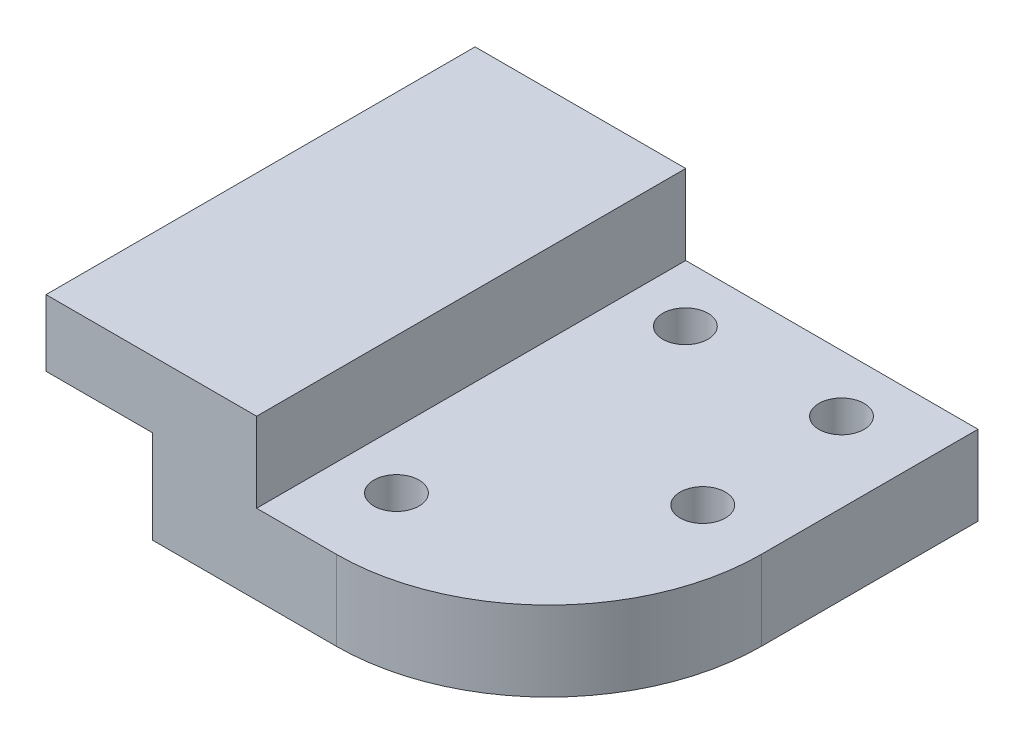
SolidWorks part; units mm, degrees
ref_plane "Front Plane" through (0, 0, 0) normal (0, 0, 1) x (1, 0, 0)
ref_plane "Top Plane" through (0, 0, 0) normal (0, 1, 0) x (1, 0, 0)
ref_plane "Right Plane" through (0, 0, 0) normal (1, 0, 0) x (0, 0, -1)
sketch "Sketch1" plane through (0, 0, 0) normal (0, 0, 1) x (1, 0, 0)
  line L0 (0, 0) -> (0, 3)
  line L1 (0, 3) -> (4, 3)
  line L3 (4, 0) -> (0, 0)
  line L4 (4, 3) -> (7.9273, 3)
  line L5 (7.9273, 3) -> (7.9273, 0)
  line L6 (7.9273, 0) -> (15.9273, 0)
  line L8 (15.9273, -3) -> (7.9273, -3)
  line L9 (7.9273, -3) -> (4, -3)
  line L10 (4, -3) -> (4, 0)
  line L11 (15.9273, 0) -> (15.9273, -3)
  dimension "D1" = 4
  dimension "D3" = 3
  dimension "D4" = 8
extrude "Boss-Extrude1" add sketch "Sketch1" along normal blind 20
ref_plane "Plane1" through (0, 0, 0) normal (0, 1, 0) x (1, 0, 0)
sketch "Sketch3" plane through (0, 0, 0) normal (0, 1, 0) x (1, 0, 0)
  line L0 (15.9273, -20) -> (15.9273, 0) construction
  line L1 (7.9273, -20) -> (15.9273, -20)
  line L2 (7.9273, -20) -> (7.9273, -12)
  line L3 (7.9273, -12) -> (15.9273, -12)
  line L4 (15.9273, -20) -> (15.9273, -12)
  dimension "D1" = 8
extrude "Cut-Extrude1" cut sketch "Sketch3" against normal blind 10
sketch "Sketch4" plane through (0, 0, 0) normal (0, 1, 0) x (1, 0, 0)
  line L0 (15.9273, -12) -> (7.9273, -12) construction
  circle A0 centre (11.9397, -3) radius 1
  circle A1 centre (11.9397, -9) radius 1
  dimension "D1" = 6
  dimension "D2" = 3
extrude "Cut-Extrude2" cut sketch "Sketch4" against normal blind 10
sketch "Sketch5" plane through (0, 0, 0) normal (0, -1, 0) x (1, 0, 0)
  line L1 (0, 20) -> (4, 20)
  line L2 (0, 20) -> (0, 0)
  line L3 (0, 0) -> (4, 0)
  line L4 (4, 20) -> (4, 0)
extrude "Cut-Extrude3" cut sketch "Sketch5" against normal blind 0.5
sketch "Sketch6" plane through (0, 0, 12) normal (0, 0, 1) x (1, 0, 0)
  line L1 (7.9273, 0) -> (15.9273, 0)
  line L2 (7.9273, 0) -> (7.9273, -3)
  line L3 (7.9273, -3) -> (15.9273, -3)
  line L4 (15.9273, 0) -> (15.9273, -3)
extrude "Boss-Extrude2" add sketch "Sketch6" along normal blind 8
extrude "Boss-Extrude3" add sketch "Sketch4<2>" against normal blind 3 contours A1
sketch "Sketch4<2>" plane through (0, 0, 0) normal (0, 1, 0) x (1, 0, 0) same geometry as "Sketch4"
sketch "Sketch7" plane through (15.9273, 0, 0) normal (1, 0, 0) x (0, 0, -1)
  line L1 (-20, 0) -> (0, 0)
  line L2 (-20, 0) -> (-20, -3)
  line L3 (-20, -3) -> (0, -3)
  line L4 (0, 0) -> (0, -3)
extrude "Boss-Extrude4" add sketch "Sketch7" along normal blind 3
sketch "Sketch8" plane through (0, 0, 20) normal (0, 0, 1) x (1, 0, 0)
  line L1 (-1.4166, 3.6124) -> (19.7203, 3.6124)
  line L2 (-1.4166, 3.6124) -> (-1.4166, -3.4619)
  line L3 (-1.4166, -3.4619) -> (19.7203, -3.4619)
  line L4 (19.7203, 3.6124) -> (19.7203, -3.4619)
extrude "Cut-Extrude4" cut sketch "Sketch8" against normal blind 3
sketch "Sketch9" plane through (0, 0, 0) normal (0, 1, 0) x (1, 0, 0)
  circle A1 centre (10.0636, -13.8735) radius 0.85
  circle A2 centre (15.9397, -3) radius 0.85
  circle A4 centre (16.218, -8.5) radius 0.85
  circle A6 centre (10.0636, -3) radius 0.85
  dimension "D2" = 5.5
extrude "Cut-Extrude6" cut sketch "Sketch9" against normal blind 3 contours A1
fillet "Fillet1" radius 8 1 edges at (18.9273, -1.5, 17)
extrude "Cut-Extrude8" cut sketch "Sketch9<5>" against normal blind 3
sketch "Sketch9<5>" plane through (0, 0, 0) normal (0, 1, 0) x (1, 0, 0) same geometry as "Sketch9"
sketch "Sketch10" plane through (0, 0, 0) normal (0, 0, -1) x (-1, 0, 0)
  line L1 (-21.548, 4.666) -> (1.1586, 4.666)
  line L2 (-21.548, 4.666) -> (-21.548, -4.2145)
  line L3 (-21.548, -4.2145) -> (1.1586, -4.2145)
  line L4 (1.1586, 4.666) -> (1.1586, -4.2145)
extrude "Cut-Extrude9" cut sketch "Sketch10" against normal blind 0.85
extrude "Boss-Extrude6" add sketch "Sketch4<3>" against normal blind 3 contours A0
sketch "Sketch4<3>" plane through (0, 0, 0) normal (0, 1, 0) x (1, 0, 0) same geometry as "Sketch4"
